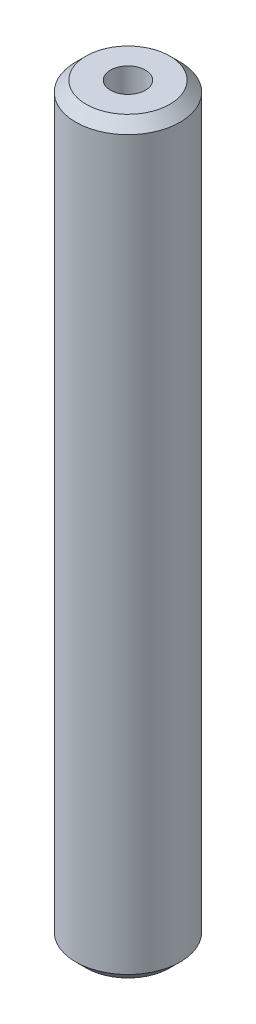
SolidWorks part; units mm, degrees
ref_plane "Front Plane" through (0, 0, 0) normal (0, 0, 1) x (1, 0, 0)
ref_plane "Top Plane" through (0, 0, 0) normal (0, 1, 0) x (1, 0, 0)
ref_plane "Right Plane" through (0, 0, 0) normal (1, 0, 0) x (0, 0, -1)
sketch "Sketch1" plane through (0, 0, 0) normal (0, 1, 0) x (1, 0, 0)
  circle A0 centre (0, 0) radius 10
  dimension "SHAFT_OD" = 20
extrude "Boss-Extrude1" add sketch "Sketch1" along normal blind 143.3579
sketch "Sketch2" plane through (0, 0, 0) normal (0, 1, 0) x (1, 0, 0)
  circle A0 centre (0, 0) radius 3.3492
  dimension "BORE_D" = 6.6984
extrude "Cut-Extrude1" cut sketch "Sketch2" along normal through all
chamfer "Chamfer1" distance 1.9805 angle 45 2 edges at (0, 143.3579, 10) (0, 0, 10)
